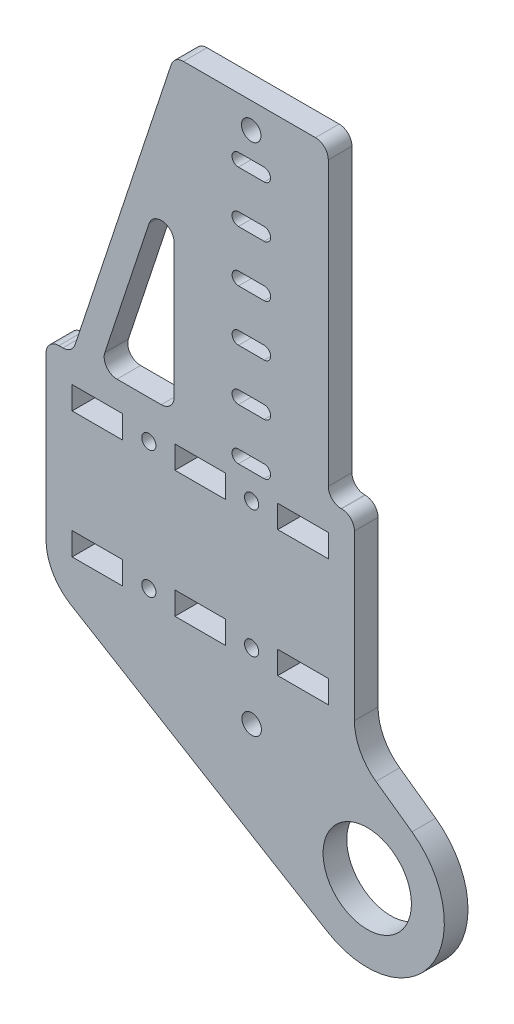
SolidWorks part; units mm, degrees
ref_plane "Front Plane" through (0, 0, 0) normal (0, 0, 1) x (1, 0, 0)
ref_plane "Top Plane" through (0, 0, 0) normal (0, 1, 0) x (1, 0, 0)
ref_plane "Right Plane" through (0, 0, 0) normal (1, 0, 0) x (0, 0, -1)
sketch "Sketch1" plane through (0, 0, 0) normal (0, 0, 1) x (1, 0, 0)
  line L0 (-38.1, 0) -> (38.1, 0) construction
  line L1 (31.65, -12.8) -> (19.15, -12.8)
  line L2 (38.1, -12.8) -> (38.1, 12.8)
  line L3 (31.65, 12.8) -> (19.15, 12.8)
  line L4 (-38.1, -12.8) -> (-38.1, 12.8)
  line L5 (38.1, -12.8) -> (-38.1, 12.8) construction
  line L6 (38.1, 12.8) -> (-38.1, -12.8) construction
  line L7 (6.25, 18.442) -> (-6.25, 18.442)
  line L8 (-19.15, -18.442) -> (-31.65, -12.8) construction
  line L9 (-19.15, -12.8) -> (-31.65, -18.442) construction
  line L10 (6.25, -12.8) -> (-6.25, -12.8)
  line L11 (-19.15, -12.8) -> (-31.65, -12.8)
  line L12 (31.65, -12.8) -> (31.65, -18.442)
  line L13 (19.15, -12.8) -> (19.15, -18.442)
  line L14 (12.6, 101.346) -> (12.6, 25.146) construction
  line L15 (-19.15, 12.8) -> (-19.15, 18.442)
  line L16 (-19.15, 18.442) -> (-31.65, 18.442)
  line L17 (-31.65, 12.8) -> (-31.65, 18.442)
  line L18 (-19.15, 12.8) -> (-31.65, 18.442) construction
  line L19 (-19.15, 18.442) -> (-31.65, 12.8) construction
  line L20 (-6.25, 12.8) -> (-6.25, 18.442)
  line L21 (6.25, 12.8) -> (6.25, 18.442)
  line L22 (31.65, 18.442) -> (19.15, 18.442)
  line L23 (19.15, 12.8) -> (19.15, 18.442)
  line L24 (31.65, 12.8) -> (31.65, 18.442)
  line L25 (-19.15, 12.8) -> (-31.65, 12.8)
  line L26 (6.25, 12.8) -> (-6.25, 12.8)
  line L27 (-38.1, 12.8) -> (-38.1, 25.146)
  line L28 (-38.1, 25.146) -> (-31.65, 25.146)
  line L29 (31.65, 25.146) -> (38.1, 25.146)
  line L30 (38.1, 25.146) -> (38.1, 12.8)
  line L31 (31.65, -18.442) -> (19.15, -18.442)
  line L32 (6.25, -12.8) -> (6.25, -18.442)
  line L33 (-6.25, -12.8) -> (-6.25, -18.442)
  line L34 (-31.65, -12.8) -> (-31.65, -18.442)
  line L35 (-19.15, -18.442) -> (-31.65, -18.442)
  line L36 (-19.15, -12.8) -> (-19.15, -18.442)
  line L37 (6.25, -18.442) -> (-6.25, -18.442)
  line L38 (31.65, -12.8) -> (19.15, -12.8)
  line L39 (-19.15, -12.8) -> (-31.65, -12.8)
  line L40 (6.25, -12.8) -> (-6.25, -12.8)
  line L41 (6.25, 12.8) -> (19.15, 12.8) construction
  line L42 (-38.1, -25.146) -> (31.4317, -67.1098)
  line L43 (38.1, -25.146) -> (52.3299, -35.2858)
  line L48 (-6.25, 12.8) -> (-19.15, 12.8) construction
  line L49 (31.65, 25.146) -> (31.65, 101.346)
  line L50 (31.65, 101.346) -> (-6.45, 101.346)
  line L51 (-6.45, 101.346) -> (-31.65, 25.146)
  line L52 (-6.45, 81.122) -> (-6.45, 25.146)
  line L53 (-6.45, 25.146) -> (-24.9618, 25.146)
  line L54 (-6.45, 81.122) -> (-24.9618, 25.146)
  line L55 (-38.1, -12.8) -> (-38.1, -25.146)
  line L56 (-0.4211, 99.3522) -> (-25.6211, 23.1522) construction
  line L58 (38.1, -12.8) -> (38.1, -25.146)
  arc A0 (31.4317, -67.1098) -> (52.3299, -35.2858) centre (41.275, -50.8) ccw
  circle A1 centre (12.7, 15.721) radius 1.7526
  circle A2 centre (-12.7, 15.721) radius 1.7526
  circle A3 centre (12.7, -15.721) radius 1.7526
  circle A4 centre (-12.7, -15.721) radius 1.7526
  circle A5 centre (12.6, 94.996) radius 2.413
  circle A6 centre (41.275, -50.8) radius 10.9125
  point P0 (0, 0)
  point P8 (-25.4, 15.621)
  point P37 (-25.4, -15.621)
  point P70 (-3.225, -28.575)
  dimension "D3" = 12.5
  dimension "D5" = 50.8
  dimension "D6" = 41.275
  dimension "D8" = 3.5052
  dimension "D13" = 3.5052
  dimension "D11" = 4.826
  dimension "D19" = 21.825
  dimension "D7" = 38.1
  dimension "D1" = 25.6
  dimension "D2" = 76.2
  dimension "D4" = 5.642
  dimension "D9" = 12.7
  dimension "D10" = 3
  dimension "D12" = 2.921
  dimension "D14" = 2.921
  dimension "D15" = 76.2
  dimension "D16" = 38.1
  dimension "D17" = 6.35
  dimension "D20" = 9.525
  dimension "D21" = 9.525
  dimension "D18" = 6.35
extrude "Boss-Extrude1" add sketch "Sketch1" along normal blind 5.842 contours L58 L2 L30 L29 L49 L50 L51 L28 L27 L4 L55 A4 L32 L37 L33 L10 L11 L36 L35 L34 L12 L31 L13 L1 L21 L26 L20 L7 L15 L25 L17 L16 L24 L3 L23 L22 region at (7.9204, 13.6342, 0)
fillet "Fillet1" radius 3.175 4 edges at (-38.1, 25.146, 2.921) (38.1, 25.146, 2.921) (-31.65, 25.146, 2.921) (31.65, 25.146, 2.921)
fillet "Fillet2" radius 3.175 3 edges at (-6.45, 25.146, 2.921) (-6.45, 81.122, 2.921) (-24.9618, 25.146, 2.921)
fillet "Fillet3" radius 3.175 2 edges at (31.65, 101.346, 2.921) (-6.45, 101.346, 2.921)
sketch "Sketch3" plane through (0, 0, 5.842) normal (0, 0, 1) x (1, 0, 0)
  line L0 (12.6, 94.996) -> (12.7, -15.721) construction
  circle A0 centre (12.7147, -32.004) radius 2.413
  dimension "D1" = 4.826
  dimension "D2" = 127
extrude "Cut-Extrude2" cut sketch "Sketch3" against normal through all
sketch "Sketch5" [suppressed] plane through (0, 0, 5.842) normal (0, 0, 1) x (1, 0, 0)
  line L1 (-55.0734, 111.0269) -> (34.825, 111.0269)
  line L2 (-55.0734, 111.0269) -> (-55.0734, 25.146)
  line L3 (-55.0734, 25.146) -> (34.825, 25.146)
  line L4 (34.825, 111.0269) -> (34.825, 25.146)
extrude "Cut-Extrude3" [suppressed] cut sketch "Sketch5" against normal through all
sketch "Sketch6" [suppressed] plane through (0, 0, 5.842) normal (0, 0, 1) x (1, 0, 0)
  line L0 (-34.925, 25.146) -> (34.925, 25.146) construction
  line L1 (31.4879, 25.146) -> (-22.4871, 25.146)
  line L2 (31.4879, 78.486) -> (34.6629, 74.676)
  line L3 (31.4879, 78.486) -> (-20.5821, 78.486)
  line L4 (-22.4871, 25.146) -> (-25.0279, 25.146)
  line L5 (34.6629, 25.146) -> (-22.4871, 78.486) construction
  line L6 (34.6629, 78.486) -> (-22.4871, 25.146) construction
  line L7 (6.0879, 25.146) -> (6.0879, 48.411) construction
  line L8 (-31.75, 25.146) -> (-22.4871, 51.816)
  line L9 (-38.1, -25.146) -> (-38.1, 21.971) construction
  line L10 (34.6629, 74.676) -> (34.6629, 41.021)
  line L11 (-31.75, 25.146) -> (-25.0279, 25.146)
  line L12 (-22.4871, 51.816) -> (-22.4871, 71.3764)
  line L13 (31.4879, 70.866) -> (31.4879, 42.926) construction
  line L14 (31.4879, 37.846) -> (31.4879, 25.146)
  line L15 (31.4879, 37.846) -> (34.6629, 41.021)
  circle A0 centre (31.4879, 70.866) radius 1.651
  circle A1 centre (31.4879, 42.926) radius 1.651
  circle A2 centre (-20.5821, 74.676) radius 1.651
  circle A3 centre (-19.3121, 27.686) radius 1.651
  arc A4 (-20.5821, 78.486) -> (-22.4871, 71.3764) centre (-20.5821, 74.676) ccw
  point P0 (6.0879, 51.816)
  point P13 (-25.7515, 23.0626)
  point P14 (-16.4886, 49.7326)
  dimension "D5" = 3.302
  dimension "D6" = 3.302
  dimension "D9" = 12.7
  dimension "D10" = 3.302
  dimension "D12" = 3.302
  dimension "D1" = 53.34
  dimension "D2" = 57.15
  dimension "D3" = 6.35
  dimension "D7" = 49.53
  dimension "D8" = 27.94
  dimension "D11" = 52.07
  dimension "D13" = 50.8
  dimension "D14" = 15.24
  dimension "D4" = 7.62
extrude "Boss-Extrude3" [suppressed] add sketch "Sketch6" against normal up to surface (5.842 mm away) up to face at (15.1277, -32.004, 0)
fillet "Fillet6" [suppressed] radius 3.175
fillet "Fillet7" [suppressed] radius 1.5875
sketch "Sketch7" [suppressed] plane through (0, 0, 5.842) normal (0, 0, 1) x (1, 0, 0)
  line L0 (20.9561, 53.086) -> (-41.1495, 53.086) construction
  line L2 (5.0811, 78.486) -> (5.0811, 25.1147) construction
  line L3 (30.7443, 78.486) -> (-20.5821, 78.486) construction
  line L4 (5.0811, 65.786) -> (5.0811, 40.386) construction
  line L5 (8.2561, 65.786) -> (8.2561, 40.386)
  line L6 (1.9061, 65.786) -> (1.9061, 40.386)
  line L7 (17.7811, 65.786) -> (17.7811, 40.386) construction
  line L8 (20.9561, 65.786) -> (20.9561, 40.386)
  line L9 (14.6061, 65.786) -> (14.6061, 40.386)
  line L10 (-24.5007, 53.086) -> (20.9561, 53.086) construction
  line L11 (-7.6189, 65.786) -> (-7.6189, 40.386) construction
  line L12 (-10.7939, 65.786) -> (-10.7939, 40.386)
  line L13 (-4.4439, 65.786) -> (-4.4439, 40.386)
  arc A0 (8.2561, 65.786) -> (1.9061, 65.786) centre (5.0811, 65.786) ccw
  arc A1 (1.9061, 40.386) -> (8.2561, 40.386) centre (5.0811, 40.386) ccw
  arc A2 (20.9561, 65.786) -> (14.6061, 65.786) centre (17.7811, 65.786) ccw
  arc A3 (14.6061, 40.386) -> (20.9561, 40.386) centre (17.7811, 40.386) ccw
  arc A4 (-10.7939, 65.786) -> (-4.4439, 65.786) centre (-7.6189, 65.786) cw
  arc A5 (-4.4439, 40.386) -> (-10.7939, 40.386) centre (-7.6189, 40.386) cw
  point P10 (5.0811, 53.086)
  point P18 (17.7811, 53.086)
  point P26 (-7.6189, 53.086)
  dimension "D2" = 3.175
  dimension "D1" = 25.4
  dimension "D3" = 25.4
  dimension "D4" = 2
extrude "Cut-Extrude4" [suppressed] cut sketch "Sketch7" against normal through all
sketch "Sketch9" [suppressed] plane through (0, 0, 5.842) normal (0, 0, 1) x (1, 0, 0)
  line L0 (-38.1, -7.52) -> (38.1, -7.52) construction
  line L1 (-38.1, -25.146) -> (-38.1, 21.971) construction
  line L2 (38.1, 21.971) -> (38.1, -25.146) construction
  line L3 (-19.15, 12.8) -> (-31.65, 12.8) construction
  text T0 "SERGE" font "Roboto Condensed" height in points 42
  dimension "D1" = 20.32
extrude "Cut-Extrude5" [suppressed] cut sketch "Sketch9" against normal blind 0.3969
sketch "Sketch10" [suppressed] plane through (0, 0, 5.842) normal (0, 0, 1) x (1, 0, 0)
  line L0 (-38.1, -4.345) -> (38.1, -4.345) construction
  line L1 (-38.1, -25.146) -> (-38.1, 21.971) construction
  line L2 (38.1, 21.971) -> (38.1, -25.146) construction
  line L3 (-19.15, 12.8) -> (-31.65, 12.8) construction
  text T0 "SERGE" font "Bebas Neue" height in points 36
  dimension "D1" = 17.145
extrude "Cut-Extrude6" [suppressed] cut sketch "Sketch10" against normal blind 0.1984
sketch "Sketch11" plane through (0, 0, 5.842) normal (0, 0, 1) x (1, 0, 0)
  line L0 (12.6, 94.996) -> (12.7, 15.721) construction
  line L1 (9.467, 61.7085) -> (15.817, 61.7085) construction
  line L2 (9.467, 63.296) -> (15.817, 63.296)
  line L3 (9.467, 60.121) -> (15.817, 60.121)
  line L4 (31.75, 55.3585) -> (-6.45, 55.3585) construction
  line L5 (-6.45, 61.4095) -> (-6.45, 28.321) construction
  line L6 (9.4508, 74.4085) -> (15.8008, 74.4085) construction
  line L7 (9.4508, 75.996) -> (15.8008, 75.996)
  line L8 (9.4508, 72.821) -> (15.8008, 72.821)
  line L9 (9.4345, 87.1085) -> (15.7845, 87.1085) construction
  line L10 (9.4345, 88.696) -> (15.7845, 88.696)
  line L11 (9.4345, 85.521) -> (15.7845, 85.521)
  line L12 (9.4345, 23.6085) -> (15.7845, 23.6085) construction
  line L13 (9.4345, 22.021) -> (15.7845, 22.021)
  line L14 (9.4345, 25.196) -> (15.7845, 25.196)
  line L15 (9.4508, 36.3085) -> (15.8008, 36.3085) construction
  line L16 (9.4508, 34.721) -> (15.8008, 34.721)
  line L17 (9.4508, 37.896) -> (15.8008, 37.896)
  line L18 (9.467, 49.0085) -> (15.817, 49.0085) construction
  line L19 (9.467, 47.421) -> (15.817, 47.421)
  line L20 (9.467, 50.596) -> (15.817, 50.596)
  arc A0 (9.467, 63.296) -> (9.467, 60.121) centre (9.467, 61.7085) ccw
  arc A1 (15.817, 60.121) -> (15.817, 63.296) centre (15.817, 61.7085) ccw
  arc A2 (9.4508, 75.996) -> (9.4508, 72.821) centre (9.4508, 74.4085) ccw
  arc A3 (15.8008, 72.821) -> (15.8008, 75.996) centre (15.8008, 74.4085) ccw
  arc A4 (9.4345, 88.696) -> (9.4345, 85.521) centre (9.4345, 87.1085) ccw
  arc A5 (15.7845, 85.521) -> (15.7845, 88.696) centre (15.7845, 87.1085) ccw
  arc A6 (9.4345, 22.021) -> (9.4345, 25.196) centre (9.4345, 23.6085) cw
  arc A7 (15.7845, 25.196) -> (15.7845, 22.021) centre (15.7845, 23.6085) cw
  arc A8 (9.4508, 34.721) -> (9.4508, 37.896) centre (9.4508, 36.3085) cw
  arc A9 (15.8008, 37.896) -> (15.8008, 34.721) centre (15.8008, 36.3085) cw
  arc A10 (9.467, 47.421) -> (9.467, 50.596) centre (9.467, 49.0085) cw
  arc A11 (15.817, 50.596) -> (15.817, 47.421) centre (15.817, 49.0085) cw
  point P6 (12.642, 61.7085)
  point P16 (12.65, 55.3585)
  point P19 (12.6258, 74.4085)
  point P26 (12.6095, 87.1085)
  point P32 (12.6095, 23.6085)
  point P39 (12.6258, 36.3085)
  point P46 (12.642, 49.0085)
  dimension "D1" = 1.5875
  dimension "D2" = 6.35
  dimension "D3" = 6.35
  dimension "D4" = 3
extrude "Cut-Extrude7" cut sketch "Sketch11" against normal through all
fillet "Fillet8" [suppressed] radius 25.4
fillet "Fillet10" radius 12.7 1 edges at (-38.1, -25.146, 2.921)
fillet "Fillet11" radius 12.7 1 edges at (38.1, -25.146, 2.921)
